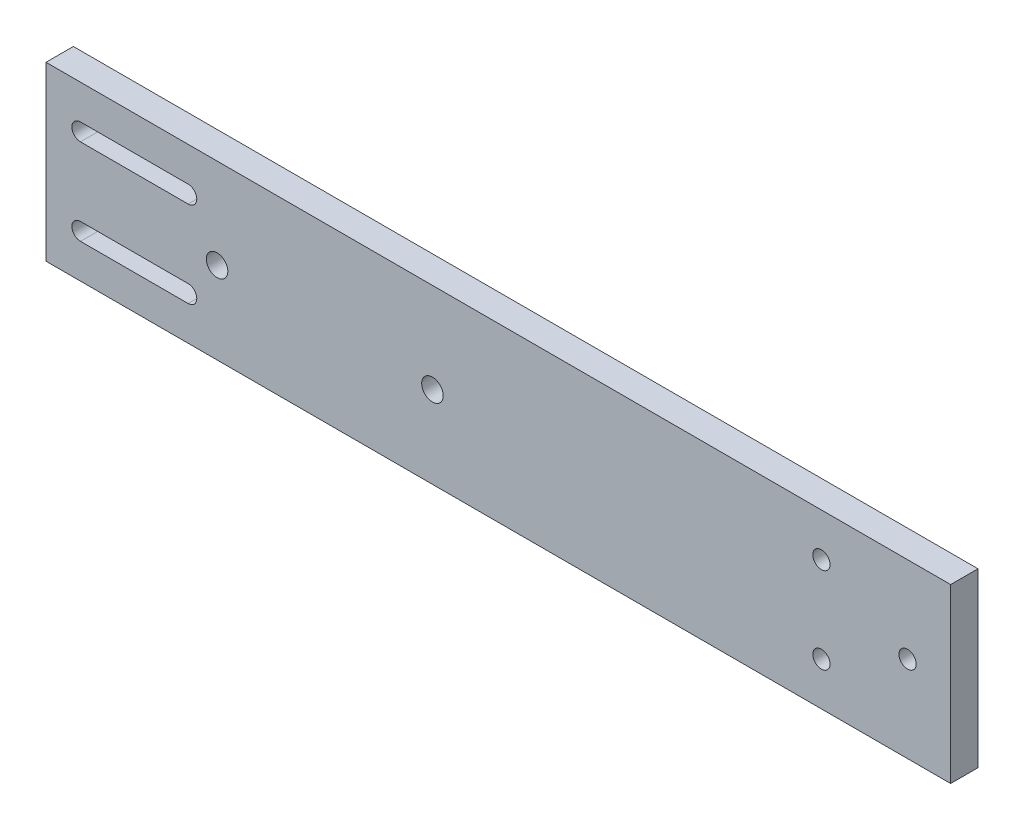
SolidWorks part; units mm, degrees
ref_plane "Front Plane" through (0, 0, 0) normal (0, 0, 1) x (1, 0, 0)
ref_plane "Top Plane" through (0, 0, 0) normal (0, 1, 0) x (1, 0, 0)
ref_plane "Right Plane" through (0, 0, 0) normal (1, 0, 0) x (0, 0, -1)
sketch "Sketch1" plane through (0, 0, 0) normal (0, 0, 1) x (1, 0, 0)
  line L0 (8, 32) -> (33, 32)
  line L1 (0, 0) -> (210, 0)
  line L2 (0, 0) -> (0, 40)
  line L3 (0, 40) -> (210, 40)
  line L4 (210, 0) -> (210, 40)
  line L5 (8, 28) -> (33, 28)
  line L6 (8, 12) -> (33, 12)
  line L7 (8, 8) -> (33, 8)
  circle A0 centre (180, 30) radius 2
  circle A1 centre (180, 10) radius 2
  circle A4 centre (200, 20) radius 2
  arc A5 (33, 32) -> (33, 28) centre (33, 30) cw
  arc A6 (8, 32) -> (8, 28) centre (8, 30) ccw
  arc A7 (33, 12) -> (33, 8) centre (33, 10) cw
  arc A8 (8, 12) -> (8, 8) centre (8, 10) ccw
  point P13 (210, 20)
  dimension "D1" = 4
  dimension "D2" = 4
  dimension "D11" = 4
  dimension "D3" = 40
  dimension "D4" = 20
  dimension "D5" = 10
  dimension "D6" = 30
  dimension "D12" = 10
  dimension "D8" = 4
  dimension "D9" = 10
  dimension "D10" = 8
  dimension "D13" = 25
  dimension "D7" = 210
  dimension "D14" = 25
  dimension "D15" = 4
  dimension "D16" = 10
extrude "Boss-Extrude1" add sketch "Sketch1" along normal blind 6.35
sketch "Sketch2" plane through (0, 0, 0) normal (0, 0, -1) x (-1, 0, 0)
  line L1 (0, 40) -> (0, 0) construction
  line L2 (0, 0) -> (-210, 0) construction
  circle A0 centre (-89.71, 19.06) radius 2.5
  circle A1 centre (-39.71, 19.06) radius 2.5
  point P8 (0, 0)
  dimension "D1" = 5
  dimension "D5" = 5
  dimension "D3" = 39.71
  dimension "D4" = 50
  dimension "D2" = 19.06
extrude "Cut-Extrude1" cut sketch "Sketch2" against normal blind 10
equation "\"D11@Sketch1\"=\"D1@Sketch1\""
equation "\"D14@Sketch1\"=\"D13@Sketch1\""
equation "\"D15@Sketch1\"=\"D8@Sketch1\""
equation "\"D16@Sketch1\"=\"D9@Sketch1\""
equation "\"D1@Sketch2\"=\"D5@Sketch2\""
